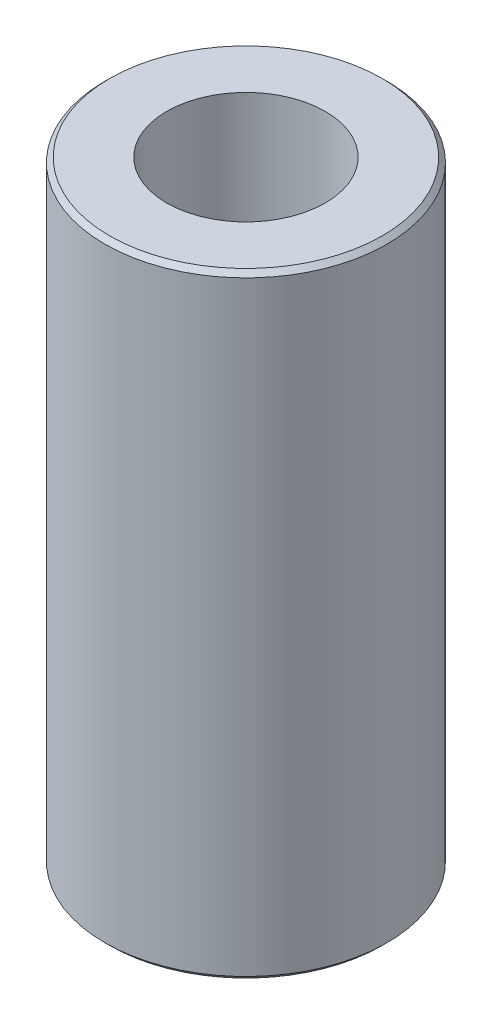
SolidWorks part; units mm, degrees
ref_plane "Front Plane" through (0, 0, 0) normal (0, 0, 1) x (1, 0, 0)
ref_plane "Top Plane" through (0, 0, 0) normal (0, 1, 0) x (1, 0, 0)
ref_plane "Right Plane" through (0, 0, 0) normal (1, 0, 0) x (0, 0, -1)
sketch "Sketch1" plane through (0, 0, 0) normal (0, 1, 0) x (1, 0, 0)
  circle A0 centre (0, 0) radius 60
  dimension "SHAFT_OD" = 120
extrude "Boss-Extrude1" add sketch "Sketch1" along normal blind 261.347
sketch "Sketch2" plane through (0, 0, 0) normal (0, 1, 0) x (1, 0, 0)
  circle A0 centre (0, 0) radius 33.7456
  dimension "BORE_D" = 67.4911
extrude "Cut-Extrude1" cut sketch "Sketch2" along normal through all
chamfer "Chamfer1" distance 2.0358 angle 45 2 edges at (0, 261.347, 60) (0, 0, 60)
